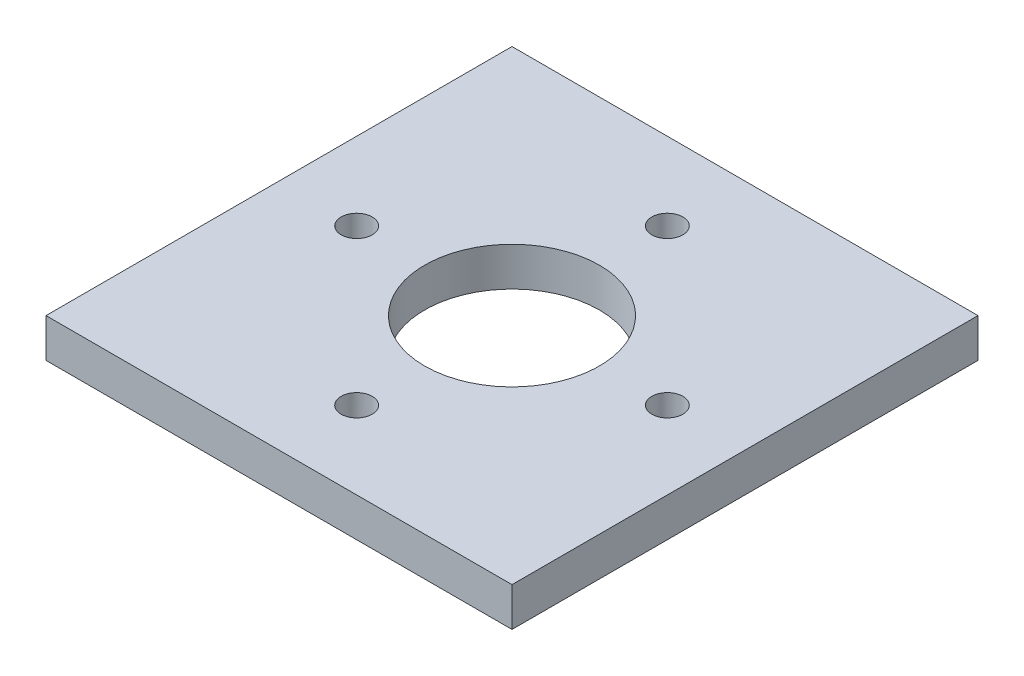
SolidWorks part; units mm, degrees
ref_plane "Front Plane" through (0, 0, 0) normal (0, 0, 1) x (1, 0, 0)
ref_plane "Top Plane" through (0, 0, 0) normal (0, 1, 0) x (1, 0, 0)
ref_plane "Right Plane" through (0, 0, 0) normal (1, 0, 0) x (0, 0, -1)
sketch "Sketch1" plane through (0, 0, 0) normal (0, 1, 0) x (1, 0, 0)
  line L1 (-38.1, -38.1) -> (38.1, -38.1)
  line L2 (-38.1, -38.1) -> (-38.1, 38.1)
  line L3 (-38.1, 38.1) -> (38.1, 38.1)
  line L4 (38.1, -38.1) -> (38.1, 38.1)
  line L5 (-38.1, -38.1) -> (38.1, 38.1) construction
  line L6 (-38.1, 38.1) -> (38.1, -38.1) construction
  circle A0 centre (0, 0) radius 14.2875
  circle A1 centre (0, 0) radius 25.4 construction
  circle A2 centre (-25.4, 0) radius 2.54
  dimension "D1" = 50.8
  dimension "D2" = 28.575
  dimension "D3" = 5.08
  dimension "D4" = 76.2
  dimension "D5" = 76.2
extrude "Initial Plate" add sketch "Sketch1" along normal blind 6.35
pattern_circular "Mounting Pattern" count 4 over 360 about axis through (0, 6.35, 0) along (0, -1, 0) reverse direction yes of face at (-25.4, 6.35, 2.54)
